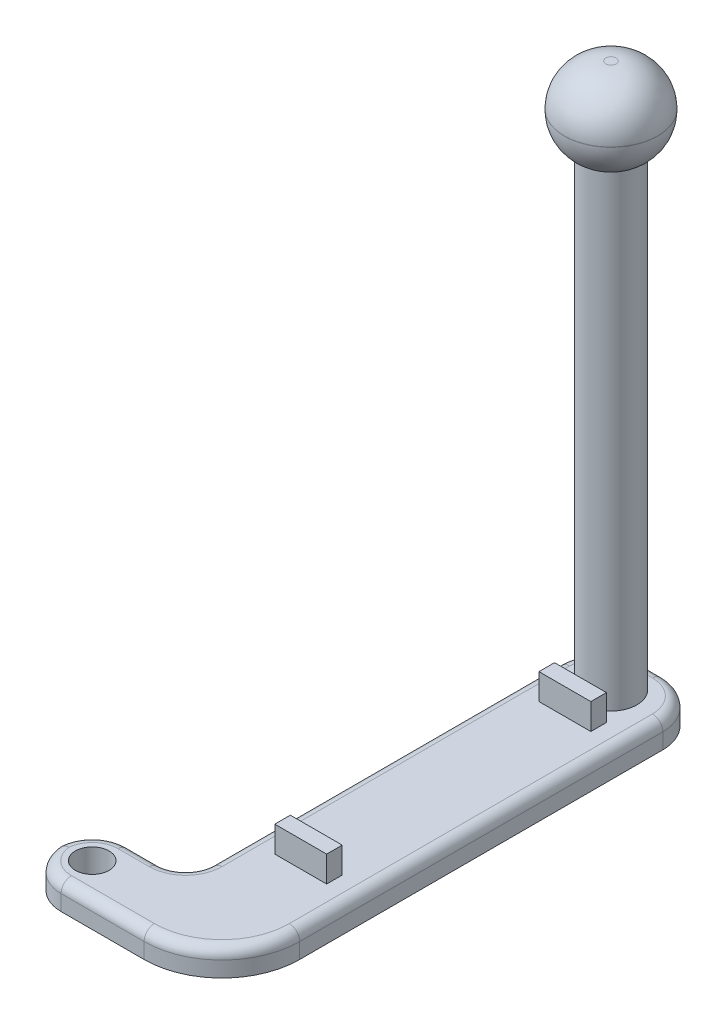
SolidWorks part; units mm, degrees
ref_plane "Front Plane" through (0, 0, 0) normal (0, 0, 1) x (1, 0, 0)
ref_plane "Top Plane" through (0, 0, 0) normal (0, 1, 0) x (1, 0, 0)
ref_plane "Right Plane" through (0, 0, 0) normal (1, 0, 0) x (0, 0, -1)
sketch "Sketch2" plane through (0, 0, 0) normal (0, 1, 0) x (1, 0, 0)
  line L0 (0, 0) -> (38, 0)
  line L1 (38, 0) -> (38, 93)
  line L2 (38, 93) -> (18, 93)
  line L3 (18, 93) -> (18, 13)
  line L4 (0, 0) -> (0, 13)
  line L5 (0, 13) -> (18, 13)
  line L7 (13, 13) -> (13, 0)
  circle A0 centre (6.5, 6.5) radius 3.25
  point P3 (13, 13)
  dimension "D1" = 38
  dimension "D2" = 93
  dimension "D3" = 18
  dimension "D4" = 80
  dimension "D5" = 5
extrude "Boss-Extrude2" add sketch "Sketch2" along normal blind 5 contours L7 L5 L4 L0 A0 | L5 L7 L0 L1 L2 L3 region at (0.1838, 0, -6.5) region at (27.5779, 0, -45.1494)
fillet "Fillet1" radius 15 1 edges at (38, 2.5, 0)
fillet "Fillet2" radius 5 1 edges at (18, 2.5, -13)
fillet "Fillet3" radius 7 2 edges at (0, 2.5, 0) (0, 2.5, -13)
fillet "Fillet4" radius 2 9 edges at (38, 5, -54) (33.6066, 5, -4.3934) (15, 5, 0) (18, 5, -55.5) (2.2303, 5, -11.1235) (10, 5, -13) (28, 5, -93) (2.2303, 5, -1.8765) (16.5355, 5, -14.4645)
fillet "Fillet5" radius 8 4 edges at (18.5858, 4.4142, -92.4142) (37.4142, 4.4142, -92.4142) (38, 1.5, -93) (18, 1.5, -93)
ref_plane "Plane1" through (0, 5, 0) normal (0, 1, 0) x (1, 0, 0)
sketch "Sketch4" plane through (0, 5, 0) normal (0, 1, 0) x (1, 0, 0)
  line L0 (28, 91) -> (28, 19.3417)
  line L1 (30, 91) -> (26, 91) construction
  line L2 (36, 85) -> (20, 85)
  circle A0 centre (28, 85) radius 5
extrude "Boss-Extrude4" add sketch "Sketch4" along normal blind 90 contours A0
ref_plane "Plane2" through (0, 95, 0) normal (0, 1, 0) x (1, 0, 0)
sketch "Sketch5" plane through (0, 95, 0) normal (0, 1, 0) x (1, 0, 0)
  circle A0 centre (28, 85) radius 9
extrude "Boss-Extrude5" add sketch "Sketch5" along normal blind 15
fillet "Fillet6" radius 8 2 edges at (28, 95, -76) (28, 110, -76)
sketch "Sketch6" plane through (0, 5, 0) normal (0, 1, 0) x (1, 0, 0)
  line L0 (36, 26.6944) -> (20, 26.6944)
  line L1 (36, 15) -> (36, 85) construction
  line L2 (20, 85) -> (20, 18) construction
  line L4 (33, 28.1944) -> (23, 28.1944)
  line L5 (33, 28.1944) -> (33, 25.1944)
  line L6 (33, 25.1944) -> (23, 25.1944)
  line L7 (23, 28.1944) -> (23, 25.1944)
  line L8 (33, 28.1944) -> (23, 25.1944) construction
  line L9 (33, 25.1944) -> (23, 28.1944) construction
  point P6 (28, 26.6944)
  dimension "D1" = 3
  dimension "D2" = 10
extrude "Boss-Extrude6" add sketch "Sketch6" along normal blind 5 contours L0 L7 L6 L5 | L4 L7 L0 L5 region at (28, 5, -25.9444) region at (28, 5, -27.4444)
sketch "Sketch7" plane through (0, 5, 0) normal (0, 1, 0) x (1, 0, 0)
  line L0 (36, 15) -> (36, 85) construction
  line L1 (36, 77.6172) -> (20, 77.6172)
  line L2 (20, 85) -> (20, 18) construction
  line L4 (23, 79.1172) -> (33, 79.1172)
  line L5 (23, 79.1172) -> (23, 76.1172)
  line L6 (23, 76.1172) -> (33, 76.1172)
  line L7 (33, 79.1172) -> (33, 76.1172)
  line L8 (23, 79.1172) -> (33, 76.1172) construction
  line L9 (23, 76.1172) -> (33, 79.1172) construction
  point P6 (28, 77.6172)
  dimension "D1" = 3
  dimension "D2" = 10
extrude "Boss-Extrude7" add sketch "Sketch7" along normal blind 5 contours L6 L7 L4 L5
